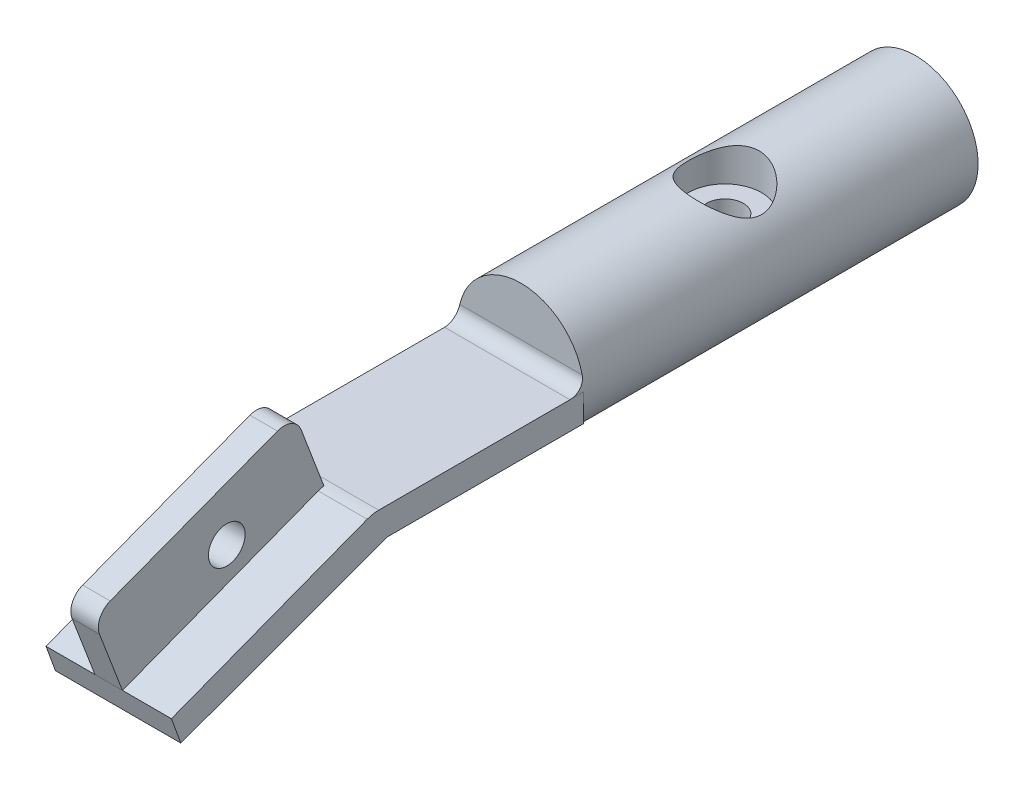
SolidWorks part; units mm, degrees
ref_plane "Front Plane" through (0, 0, 0) normal (0, 0, 1) x (1, 0, 0)
ref_plane "Top Plane" through (0, 0, 0) normal (0, 1, 0) x (1, 0, 0)
ref_plane "Right Plane" through (0, 0, 0) normal (1, 0, 0) x (0, 0, -1)
sketch "Sketch1" plane through (0, 0, 0) normal (1, 0, 0) x (0, 0, -1)
  line L0 (-21.8523, 0) -> (24.1477, 0)
  line L1 (24.1477, 0) -> (24.1477, 6)
  line L2 (24.1477, 6) -> (-21.8523, 6)
  line L3 (-21.8523, 6) -> (-21.8523, 0)
  dimension "D1" = 46
  dimension "D2" = 6
extrude "Boss-Extrude1" add sketch "Sketch1" against normal blind 27.35
sketch "Sketch2" plane through (0, 0, 0) normal (1, 0, 0) x (0, 0, -1)
  line L0 (-21.8523, 6) -> (-65.7553, -10.7788)
  line L1 (24.1477, 6) -> (-21.8523, 6) construction
  line L2 (-18.5979, 0) -> (-63.7032, -16.417)
  line L3 (-65.7553, -10.7788) -> (-63.7032, -16.417)
  line L4 (-21.8523, 0) -> (24.1477, 0) construction
  line L5 (-21.8523, 6) -> (-18.5979, 0)
  dimension "D1" = 160
  dimension "D2" = 6
  dimension "D3" = 48
  dimension "D4" = 47
extrude "Boss-Extrude2" add sketch "Sketch2" against normal blind 27.35
fillet "Fillet1" radius 7 1 edges at (-13.675, 6, 21.8523)
sketch "Sketch3" plane through (0, 0, -24.1477) normal (0, 0, -1) x (-1, 0, 0)
  line L0 (27.35, 6) -> (0, 6) construction
  line L1 (0, 6) -> (27.35, 6)
  circle A0 centre (13.675, 6) radius 13.675
  line M3 (0, 0) -> (27.35, 0)
  line M5 (27.35, 6) -> (0, 6)
extrude "Boss-Extrude3" add sketch "Sketch3" along normal blind 86 contours A0 M5 | A0 M3 | A0 M5 M3 region at (-13.675, 11.8039, -24.1477) region at (-13.675, 3.0519, -24.1477) region at (-13.675, -3.1584, -24.1477)
fillet "Fillet2" radius 3 1 edges at (-13.675, 6, -24.1477)
sketch "Sketch5" plane through (0, 0, 0) normal (0, 1, 0) x (1, 0, 0)
  line L0 (0, 110.1477) -> (-27.35, 110.1477) construction
  circle A0 centre (-12.2031, 67.1477) radius 8
  circle A1 centre (-12.2031, 67.1477) radius 4
  dimension "D1" = 43
  dimension "D2" = 16
extrude "Cut-Extrude1" cut sketch "Sketch5" along normal through all
sketch "Sketch6" plane through (0, 0, 0) normal (0, 1, 0) x (1, 0, 0)
  circle A0 centre (-12.2031, 67.1477) radius 4
extrude "Cut-Extrude2" cut sketch "Sketch6" along normal through all
sketch "Sketch7" plane through (0, 0, 0) normal (0, 1, 0) x (1, 0, 0)
  circle A0 centre (-12.2031, 67.1477) radius 4
extrude "Cut-Extrude3" cut sketch "Sketch7" against normal through all
sketch "Sketch8" plane through (0, 0, 0) normal (0, 1, 0) x (1, 0, 0)
  circle A0 centre (-12.2031, 67.1477) radius 8
  circle A1 centre (-12.2031, 67.1477) radius 4
extrude "Boss-Extrude4" add sketch "Sketch8" along normal blind 6
sketch "Sketch9" plane through (0, 6, 0) normal (0, 1, 0) x (1, 0, 0)
  circle A0 centre (-12.2031, 67.1477) radius 8
  circle A1 centre (-12.2031, 67.1477) radius 4
extrude "Boss-Extrude5" add sketch "Sketch9" along normal blind 6
move or copy body "Body-Move/Copy1" bodies to move or copy 108 copy no translate (13.675, 0, 0) parameters "D1"=13.675, "D2"=0, "D3"=0
sketch "Sketch11" plane through (0, 0, 0) normal (1, 0, 0) x (0, 0, -1)
  line L0 (-65.7553, -10.7788) -> (-21.8308, 5.8837)
  line L1 (-21.8308, 5.8837) -> (-26.7964, 18.9735)
  line L2 (-31.9551, 21.2947) -> (-68.432, 7.4574)
  line L3 (-70.7497, 2.2895) -> (-65.7553, -10.7788)
  arc A0 (-20.5602, 6) -> (-23.0592, 5.5387) centre (-20.5602, -1) ccw construction
  arc A1 (-31.9551, 21.2947) -> (-26.7964, 18.9735) centre (-30.5363, 17.5548) cw
  arc A2 (-68.432, 7.4574) -> (-70.7497, 2.2895) centre (-67.0133, 3.7174) ccw
  circle A3 centre (-43.0133, 5.335) radius 4
  dimension "D1" = 4
  dimension "D2" = 20
  dimension "D3" = 7
  dimension "D4" = 14
extrude "Boss-Extrude6" add sketch "Sketch11" along normal mid plane 6
